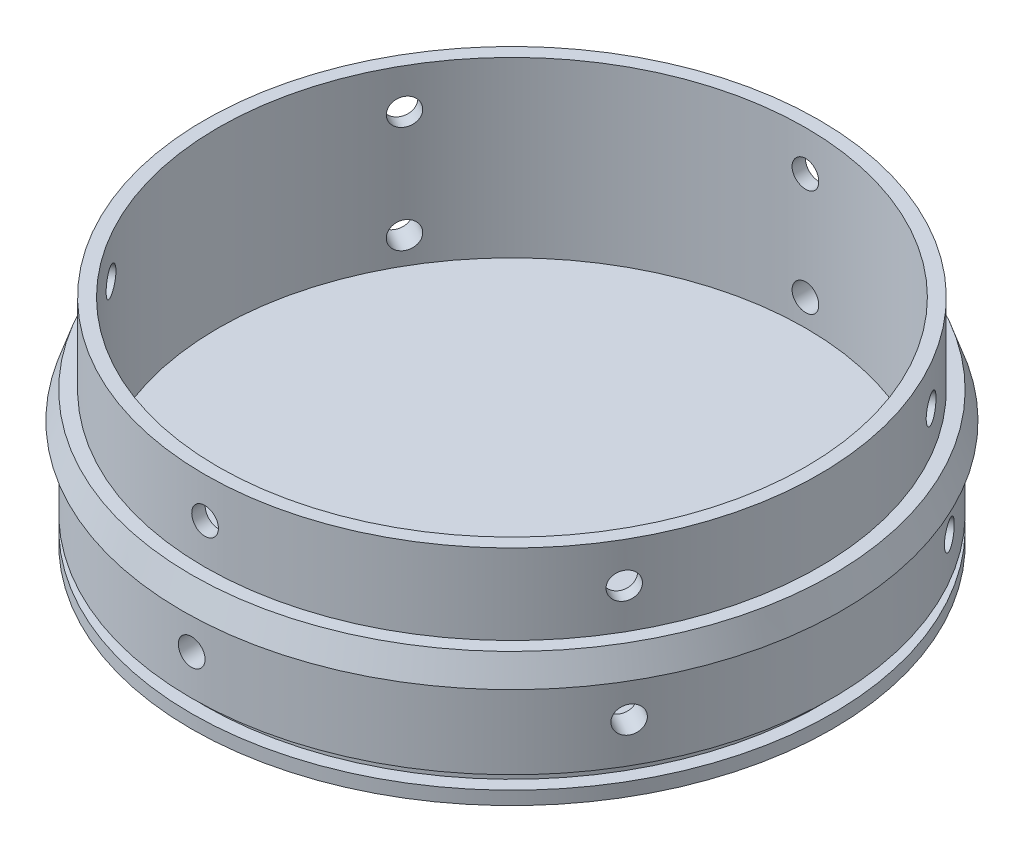
SolidWorks part; units mm, degrees
material "2024-T4"
ref_plane "Front Plane" through (0, 0, 0) normal (0, 0, 1) x (1, 0, 0)
ref_plane "Top Plane" through (0, 0, 0) normal (0, 1, 0) x (1, 0, 0)
ref_plane "Right Plane" through (0, 0, 0) normal (1, 0, 0) x (0, 0, -1)
sketch "Sketch1" plane through (0, 0, 0) normal (0, 1, 0) x (1, 0, 0)
  circle A0 centre (0, 0) radius 78.359
  circle A2 centre (0, 0) radius 76.2
  circle A3 centre (0, 0) radius 73.025
  dimension "D1" = 156.718
  dimension "D2" = 152.4
  dimension "D3" = 3.175
extrude "Boss-Extrude1" add sketch "Sketch1" along normal blind 6.35 contours A0 A2 region at (-78.1374, 0, 0)
extrude "Boss-Extrude2" add sketch "Sketch1<3>" along normal blind 25.4 contours A2 A3 region at (-74.0447, 0, 0)
sketch "Sketch1<3>" plane through (0, 0, 0) normal (0, 1, 0) x (1, 0, 0) same geometry as "Sketch1"
sketch "Sketch2" plane through (0, 0, 0) normal (0, -1, 0) x (1, 0, 0)
  circle A0 centre (0, 0) radius 73.025 construction
  circle A1 centre (0, 0) radius 73.025
  circle A2 centre (0, 0) radius 76.2
  dimension "D1" = 3.175
extrude "Boss-Extrude3" add sketch "Sketch2" along normal blind 25.4
sketch "Sketch3" plane through (0, -25.4, 0) normal (0, -1, 0) x (1, 0, 0)
  circle A1 centre (0, 0) radius 76.2
  circle A2 centre (0, 0) radius 76.2
  dimension "D1" = 0
extrude "Boss-Extrude4" add sketch "Sketch3" against normal blind 9.525
sketch "Sketch5" plane through (0, 0, 0) normal (0, 0, 1) x (1, 0, 0)
  line L0 (-76.2, -25.4) -> (76.2, -25.4) construction
  line L1 (-76.2, 0) -> (-76.2, -25.4) construction
  line L2 (-76.2, -25.4) -> (76.2, -25.4)
  line L3 (-76.2, 0) -> (-76.2, -25.4)
  line L4 (-76.2, -22.225) -> (-73.025, -22.225)
  line L5 (-73.025, -22.225) -> (-73.025, -19.05)
  line L6 (-73.025, -19.05) -> (-76.2, -19.05)
  line L7 (0, 0) -> (0, -25.4) construction
  dimension "D1" = 3.175
  dimension "D2" = 3.175
  dimension "D3" = 3.175
revolve "Cut-Revolve1" cut sketch "Sketch5" angle 360 about L7 region at (-74.6125, -20.6375, 0)
ref_plane "Plane1" through (0, 0, 76.2) normal (0, 0, 1) x (1, 0, 0)
chamfer "Chamfer1" distance 6.35 distance2 2.159 1 edges at (0, 6.35, 78.359) first distance on face at (0, 6.35, 78.359)
sketch "Sketch6" plane through (0, 25.4, 0) normal (0, 1, 0) x (1, 0, 0)
  circle A1 centre (0, 0) radius 76.2
  circle A2 centre (0, 0) radius 76.2
  dimension "D1" = 0
extrude "Cut-Extrude1" cut sketch "Sketch6" against normal blind 19.05
sketch "Sketch7" plane through (0, -15.875, 0) normal (0, 1, 0) x (1, 0, 0)
  circle A0 centre (0, 0) radius 69.85
  circle A1 centre (0, 0) radius 73.025
  dimension "D1" = 146.05
  dimension "D2" = 139.7
extrude "Boss-Extrude5" add sketch "Sketch7" along normal blind 41.275
sketch "Sketch8" plane through (0, 0, 76.2) normal (0, 0, 1) x (1, 0, 0)
  line L0 (76.2, 6.35) -> (-76.2, 6.35) construction
  line L1 (76.2, 6.35) -> (-76.2, 6.35)
  circle A0 centre (0, -9.525) radius 3.175
  circle A1 centre (0, 15.875) radius 3.175
  point P4 (0, 0)
  point P7 (0, 0)
  dimension "D1" = 6.35
  dimension "D2" = 6.35
  dimension "D3" = 9.525
  dimension "D4" = 9.525
extrude "Cut-Extrude2" cut sketch "Sketch8" against normal up to next contours A1 | A0 region at (0, -9.525, 76.2) region at (0, 15.875, 76.2)
pattern_circular "CirPattern1" count 6 over 360 about axis through (0, 25.4, 0) along (0, -1, 0) of "Cut-Extrude2" reverse direction yes
